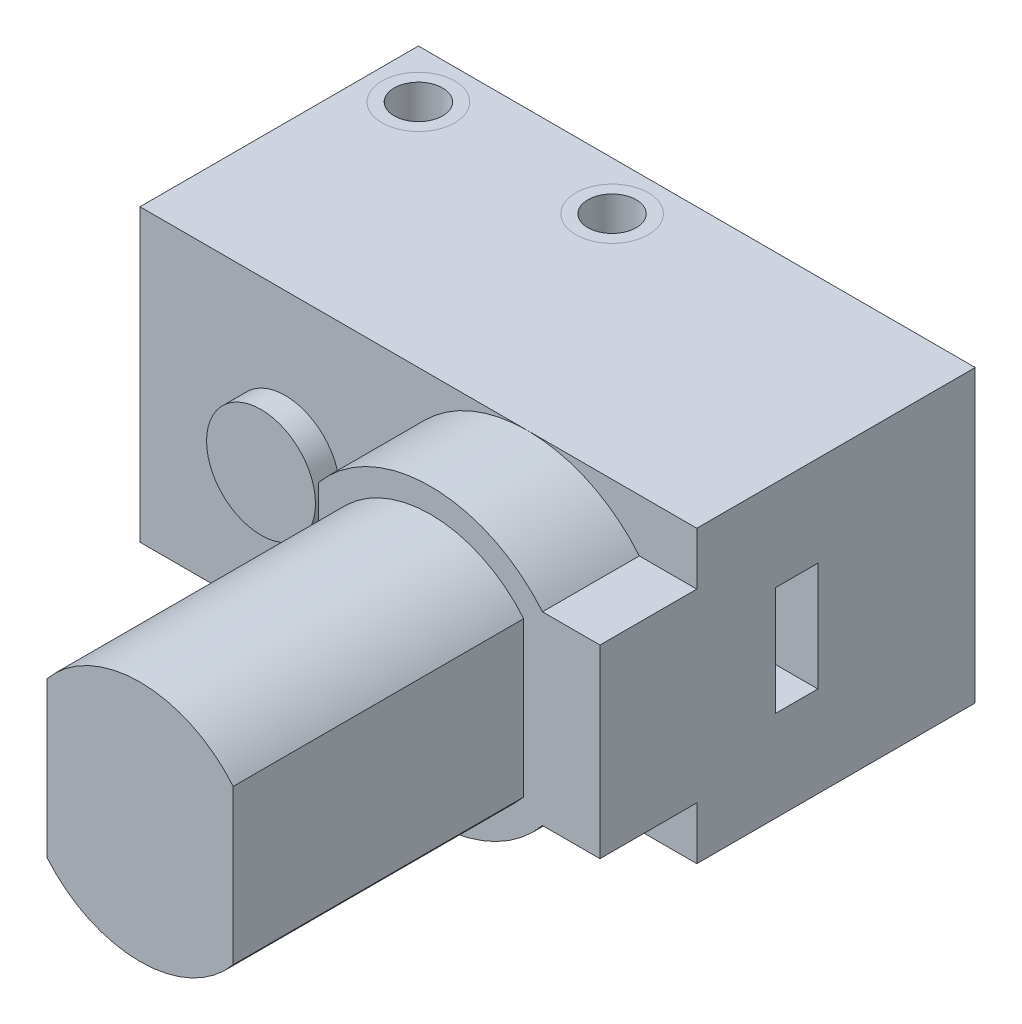
SolidWorks part; units mm, degrees
ref_plane "前视基准面" through (0, 0, 0) normal (0, 0, 1) x (1, 0, 0)
ref_plane "上视基准面" through (0, 0, 0) normal (0, 1, 0) x (1, 0, 0)
ref_plane "右视基准面" through (0, 0, 0) normal (1, 0, 0) x (0, 0, -1)
other "Configuration Table"
sketch "草图1" plane through (0, 0, 0) normal (0, 1, 0) x (1, 0, 0)
  line L1 (-23, -11.5) -> (23, -11.5)
  line L2 (-23, -11.5) -> (-23, 11.5)
  line L3 (-23, 11.5) -> (23, 11.5)
  line L4 (23, -11.5) -> (23, 11.5)
  line L5 (-23, -11.5) -> (23, 11.5) construction
  line L6 (-23, 11.5) -> (23, -11.5) construction
  point P0 (0, 0)
  dimension "D1" = 23
  dimension "D2" = 46
extrude "凸台-拉伸1" add sketch "草图1" along normal blind 24
sketch "草图2" plane through (0, 0, 11.5) normal (0, 0, 1) x (1, 0, 0)
  line L0 (-23, 0) -> (23, 0) construction
  line L1 (-23, 24) -> (23, 24) construction
  line L2 (23, 24) -> (23, 0) construction
  line L3 (-0.25, 19.6444) -> (-0.25, 4.3556)
  line L5 (9, 12) -> (9, 0) construction
  line L6 (18.25, 19.6444) -> (23, 19.6444)
  line L7 (18.25, 4.3556) -> (23, 4.3556)
  line L8 (23, 4.3556) -> (23, 19.6444)
  line L9 (9, 12) -> (23, 12) construction
  arc A0 (-0.25, 4.3556) -> (18.25, 4.3556) centre (9, 12) ccw
  arc A1 (18.25, 19.6444) -> (-0.25, 19.6444) centre (9, 12) ccw
  dimension "D1" = 14
  dimension "D2" = 9.25
  dimension "D3" = 15.2889
extrude "凸台-拉伸2" add sketch "草图2" along normal blind 8
sketch "草图3" plane through (0, 0, 19.5) normal (0, 0, 1) x (1, 0, 0)
  line L0 (1.3, 18.3804) -> (1.3, 5.6196)
  line L1 (16.7, 18.3804) -> (16.7, 5.6196)
  arc A0 (16.7, 18.3804) -> (1.3, 18.3804) centre (9, 12) ccw
  arc A1 (18.25, 19.6444) -> (9, 24) centre (9, 12) ccw construction
  arc A2 (1.3, 5.6196) -> (16.7, 5.6196) centre (9, 12) ccw
  dimension "D1" = 20
  dimension "D2" = 15.4
  dimension "D3" = 7.7
extrude "凸台-拉伸3" add sketch "草图3" along normal blind 24
sketch "草图4" plane through (0, 0, 11.5) normal (0, 0, 1) x (1, 0, 0)
  line L1 (-23, 24) -> (-23, 0) construction
  line L2 (-0.25, 19.6444) -> (-0.25, 4.3556) construction
  circle A0 centre (-11, 12) radius 4.5
  circle A1 centre (-0.25, 12) radius 2
  point P2 (-23, 12)
  dimension "D3" = 9
  dimension "D4" = 4
  dimension "D1" = 24
  dimension "D2" = 12
extrude "凸台-拉伸4" add sketch "草图4" along normal blind 2
sketch "草图6" plane through (23, 0, 0) normal (1, 0, 0) x (0, 0, -1)
  line L0 (11.5, 24) -> (11.5, 0) construction
  line L1 (-5, 16.5) -> (-1.5, 16.5)
  line L2 (-5, 16.5) -> (-5, 7.5)
  line L3 (-5, 7.5) -> (-1.5, 7.5)
  line L4 (-1.5, 16.5) -> (-1.5, 7.5)
  line L5 (-5, 16.5) -> (-1.5, 7.5) construction
  line L6 (-5, 7.5) -> (-1.5, 16.5) construction
  line L7 (-19.5, 4.3556) -> (-19.5, 19.6444) construction
  point P4 (-3.25, 12)
  point P5 (11.5, 12)
  dimension "D1" = 13
  dimension "D2" = 14.5
  dimension "D3" = 9
  dimension "D4" = 3.5
extrude "切除-拉伸1" cut sketch "草图6" against normal blind 5
sketch "草图7" plane through (0, 0, -11.5) normal (0, 0, -1) x (-1, 0, 0)
  circle A0 centre (11, 12) radius 2.7
  circle A1 centre (11, 12) radius 4.5 construction
  dimension "D1" = 5.4
extrude "凸台-拉伸5" add sketch "草图7" along normal blind 2
sketch "草图8" plane through (0, 0, -13.5) normal (0, 0, -1) x (-1, 0, 0)
  line L0 (9.25, 14.0561) -> (9.25, 9.9439)
  line L1 (12.75, 14.0561) -> (12.75, 9.9439)
  circle A0 centre (11, 12) radius 2.7 construction
  arc A1 (9.25, 9.9439) -> (12.75, 9.9439) centre (11, 12) ccw
  arc A2 (12.75, 14.0561) -> (9.25, 14.0561) centre (11, 12) ccw
  point P4 (11, 12)
  dimension "D1" = 3.5
  dimension "D2" = 1.75
extrude "凸台-拉伸6" add sketch "草图8" along normal blind 7
sketch "草图9" plane through (0, 0, -20.5) normal (0, 0, -1) x (-1, 0, 0)
  circle A0 centre (11, 12) radius 1.25
  dimension "D1" = 2.5
extrude "切除-拉伸2" cut sketch "草图9" against normal blind 5
sketch "草图10" plane through (0, 24, 0) normal (0, 1, 0) x (1, 0, 0)
  line L0 (23, 11.5) -> (-23, 11.5) construction
  line L1 (-23, 11.5) -> (-23, -11.5) construction
  circle A0 centre (-19, 7.5) radius 3
  circle A1 centre (-3, 7.5) radius 3
  dimension "D5" = 6
  dimension "D1" = 16
  dimension "D2" = 4
  dimension "D3" = 4
extrude "切除-拉伸3" cut sketch "草图10" against normal blind 8
extrude "切除-拉伸4" cut sketch "草图10<2>" along normal blind 8 from surface starting at face at (1.8, 0, 2.3)
sketch "草图10<2>" plane through (0, 24, 0) normal (0, 1, 0) x (1, 0, 0) same geometry as "草图10"
sketch "草图11" plane through (0, 0, -11.5) normal (0, 0, -1) x (-1, 0, 0)
  line L0 (12.75, 12) -> (-23, 12) construction
  line L1 (12.75, 9.9439) -> (12.75, 14.0561) construction
  line L2 (-23, 24) -> (-23, 0) construction
  circle A0 centre (-13, 20) radius 2
  circle A1 centre (-13, 4) radius 2
  dimension "D1" = 4
  dimension "D2" = 10
  dimension "D3" = 16
extrude "切除-拉伸5" cut sketch "草图11" against normal blind 8
sketch "Sketch1" plane through (0, 24, 0) normal (0, 1, 0) x (1, 0, 0)
  circle A0 centre (-19, 7.5) radius 2
  circle A1 centre (-3, 7.5) radius 2
  circle A2 centre (-3, 7.5) radius 3 construction
  circle A3 centre (-19, 7.5) radius 3 construction
  circle A4 centre (-3, 7.5) radius 3
  circle A5 centre (-19, 7.5) radius 3
  circle M1 centre (-19, 7.5) radius 3
  circle M2 centre (-3, 7.5) radius 3
  dimension "D1" = 4
  dimension "D2" = 4
extrude "Boss-Extrude1" add sketch "Sketch1" against normal up to surface (8 mm away) separate body up to face at (-19, 16, -4.5)
extrude "Boss-Extrude2" add sketch "Sketch1<2>" along direction (0, -1, 0) on the side of the normal up to surface (-16 mm away) from surface separate body contours A1 M2 | A0 M1 region at (-5.9151, 24, -7.5) region at (-21.9151, 24, -7.5) up to face at (-19, 8, -10.5) starting at face at (-19, 0, -10.5)
sketch "Sketch1<2>" plane through (0, 24, 0) normal (0, 1, 0) x (1, 0, 0) same geometry as "Sketch1"
equation "\"D3@草图3\"=\"D2@草图3\"/2"
equation "\"D2@草图4\"=\"D1@草图4\"/2"
